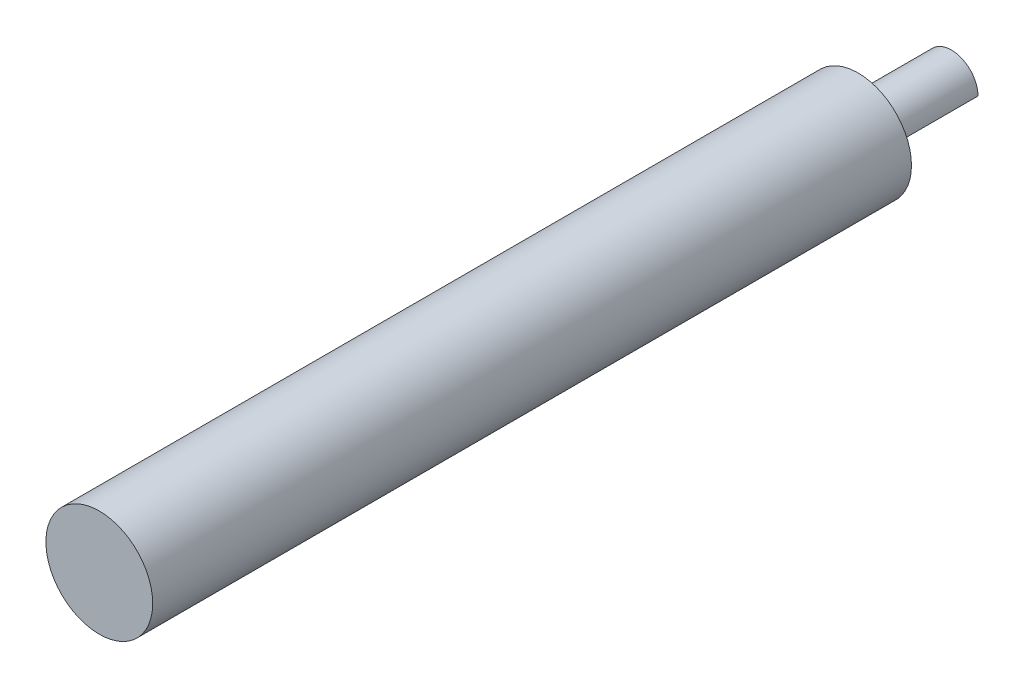
SolidWorks part; units mm, degrees
ref_plane "Front Plane" through (0, 0, 0) normal (0, 0, 1) x (1, 0, 0)
ref_plane "Top Plane" through (0, 0, 0) normal (0, 1, 0) x (1, 0, 0)
ref_plane "Right Plane" through (0, 0, 0) normal (1, 0, 0) x (0, 0, -1)
sketch "Sketch1" plane through (0, 0, 0) normal (0, 0, 1) x (1, 0, 0)
  circle A0 centre (0, 0) radius 3.1623
  dimension "D1" = 6.3246
extrude "Boss-Extrude1" add sketch "Sketch1" along normal blind 11.0998
sketch "Sketch2" plane through (0, 0, 0) normal (0, 0, -1) x (-1, 0, 0)
  line L0 (0.0012, -3.1623) -> (-3.1623, 0.0012)
  circle A0 centre (0, 0) radius 3.1623 construction
  dimension "D1" = 2.2352
extrude "Cut-Extrude1" cut sketch "Sketch2" against normal through all and the other way through all
sketch "Sketch3" plane through (0, 0, 11.0998) normal (0, 0, 1) x (1, 0, 0)
  circle A0 centre (0, 0) radius 6.35
  dimension "D1" = 12.7
extrude "Boss-Extrude2" add sketch "Sketch3" along normal blind 90.2208
